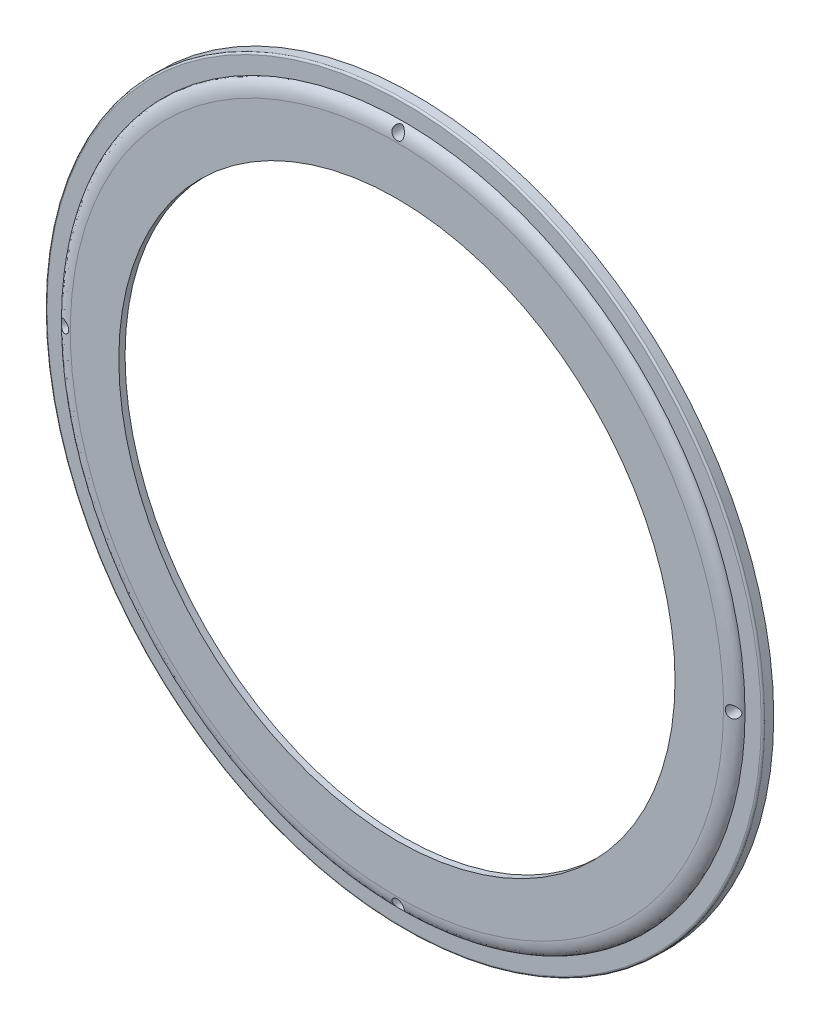
SolidWorks part; units mm, degrees
ref_plane "Plano frontal" through (0, 0, 0) normal (0, 0, 1) x (1, 0, 0)
ref_plane "Plano superior" through (0, 0, 0) normal (0, 1, 0) x (1, 0, 0)
ref_plane "Plano direito" through (0, 0, 0) normal (1, 0, 0) x (0, 0, -1)
sketch "Esboço1" plane through (0, 0, 0) normal (0, 0, 1) x (1, 0, 0)
  circle A0 centre (0, 0) radius 100 construction
  circle A1 centre (0, 0) radius 100
  circle A2 centre (-93.125, 0) radius 1.65 construction
  circle A3 centre (-93.125, 0) radius 1.65
  circle A4 centre (0, 93.125) radius 1.65 construction
  circle A5 centre (0, 93.125) radius 1.65
  circle A6 centre (93.125, 0) radius 1.65 construction
  circle A7 centre (93.125, 0) radius 1.65
  circle A8 centre (0, -93.125) radius 1.65 construction
  circle A9 centre (0, -93.125) radius 1.65
  circle A10 centre (0, 0) radius 82.5 construction
  circle A11 centre (0, 0) radius 82.5 construction
  circle A12 centre (0, 0) radius 84
  dimension "D1" = 1.5
extrude "Ressalto-extrusão1" add sketch "Esboço1" along normal blind 3
sketch "Esboço2" plane through (0, 0, 3) normal (0, 0, 1) x (1, 0, 0)
  circle A0 centre (0, 0) radius 95
  circle A1 centre (0, 0) radius 77.5
  circle A2 centre (93.125, 0) radius 1.65 construction
  circle A3 centre (0, 93.125) radius 1.65 construction
  circle A4 centre (-93.125, 0) radius 1.65 construction
  circle A5 centre (0, -93.125) radius 1.65 construction
  circle A6 centre (93.125, 0) radius 1.65
  circle A7 centre (0, 93.125) radius 1.65
  circle A8 centre (-93.125, 0) radius 1.65
  circle A9 centre (0, -93.125) radius 1.65
  dimension "D1" = 155
  dimension "D2" = 190
extrude "Ressalto-extrusão5" add sketch "Esboço2" along normal blind 2
fillet "Filete1" radius 2 1 edges at (95, 0, 5) second distance 4 first distance on face at (95, 0, 5)
fillet "Filete2" radius 0.5 1 edges at (100, 0, 3)
sketch "Esboço3" plane through (0, 0, 3) normal (0, 0, -1) x (-1, 0, 0)
  circle A1 centre (0, 0) radius 84
  circle A2 centre (0, 0) radius 84
  dimension "D1" = 0
extrude "Corte-extrusão1" cut sketch "Esboço3" against normal blind 0.25
fillet "Filete3" radius 3.25 1 edges at (84, 0, 0)
